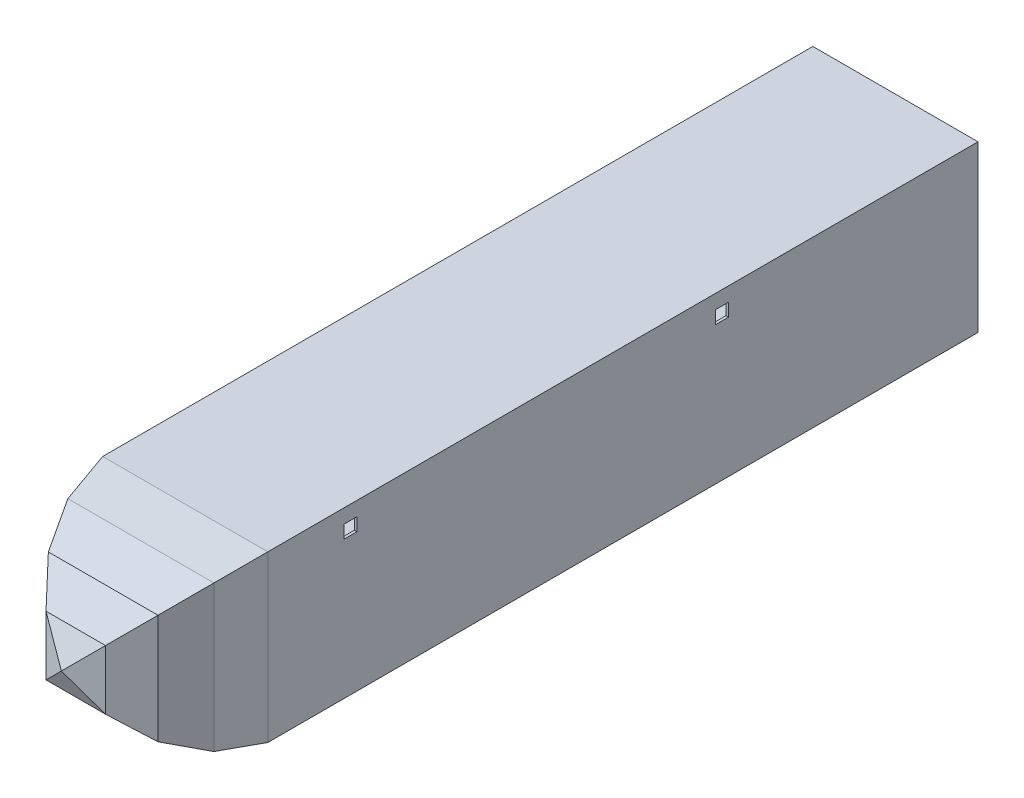
SolidWorks part; units mm, degrees
ref_plane "Front Plane" through (0, 0, 0) normal (0, 0, 1) x (1, 0, 0)
ref_plane "Top Plane" through (0, 0, 0) normal (0, 1, 0) x (1, 0, 0)
ref_plane "Right Plane" through (0, 0, 0) normal (1, 0, 0) x (0, 0, -1)
sketch "Sketch1" plane through (0, 0, 0) normal (0, 0, 1) x (1, 0, 0)
  line L1 (-50.8, -50.8) -> (50.8, -50.8)
  line L2 (-50.8, -50.8) -> (-50.8, 50.8)
  line L3 (-50.8, 50.8) -> (50.8, 50.8)
  line L4 (50.8, -50.8) -> (50.8, 50.8)
  line L5 (-50.8, -50.8) -> (50.8, 50.8) construction
  line L6 (-50.8, 50.8) -> (50.8, -50.8) construction
  point P0 (0, 0)
  dimension "D1" = 101.6
  dimension "D2" = 101.6
extrude "Boss-Extrude1" add sketch "Sketch1" along normal blind 436.88 contours L2 L1 L4 L3
ref_plane "Plane1" through (0, 0, 464.1566) normal (0, 0, 1) x (1, 0, 0)
sketch "Sketch3" plane through (0, 0, 464.1566) normal (0, 0, 1) x (1, 0, 0)
  line L1 (-44.9132, -44.9132) -> (44.9132, -44.9132)
  line L2 (-44.9132, -44.9132) -> (-44.9132, 44.9132)
  line L3 (-44.9132, 44.9132) -> (44.9132, 44.9132)
  line L4 (44.9132, -44.9132) -> (44.9132, 44.9132)
  line L5 (-44.9132, -44.9132) -> (44.9132, 44.9132) construction
  line L6 (-44.9132, 44.9132) -> (44.9132, -44.9132) construction
  point P0 (0, 0)
  dimension "D1" = 89.8265
  dimension "D2" = 89.8265
sketch "Sketch5" plane through (0, 0, 436.88) normal (0, 0, 1) x (1, 0, 0)
  line L0 (50.8, -50.8) -> (50.8, 50.8) construction
  line L1 (-50.8, 50.8) -> (50.8, 50.8) construction
  line L2 (-50.8, -50.8) -> (-50.8, 50.8) construction
  line L3 (-50.8, -50.8) -> (50.8, -50.8) construction
  line L4 (50.8, -50.8) -> (50.8, 50.8)
  line L5 (-50.8, 50.8) -> (50.8, 50.8)
  line L6 (-50.8, -50.8) -> (-50.8, 50.8)
  line L7 (-50.8, -50.8) -> (50.8, -50.8)
loft "Loft2" add profiles "Sketch5", "Sketch3" connector at (-50.8, 50.8, 436.88) connector at (-44.9132, 44.9132, 464.1566)
ref_plane "Plane2" through (0, 0, 487.3594) normal (0, 0, 1) x (1, 0, 0)
sketch "Sketch6" plane through (0, 0, 487.3594) normal (0, 0, 1) x (1, 0, 0)
  line L1 (-33.7159, -33.7159) -> (33.7159, -33.7159)
  line L2 (-33.7159, -33.7159) -> (-33.7159, 33.7159)
  line L3 (-33.7159, 33.7159) -> (33.7159, 33.7159)
  line L4 (33.7159, -33.7159) -> (33.7159, 33.7159)
  line L5 (-33.7159, -33.7159) -> (33.7159, 33.7159) construction
  line L6 (-33.7159, 33.7159) -> (33.7159, -33.7159) construction
  point P0 (0, 0)
  dimension "D1" = 67.4318
  dimension "D2" = 67.4318
loft "Loft3" add profiles "Sketch3<6>", "Sketch6" connector at (-44.9132, 44.9132, 464.1566) connector at (-33.7159, 33.7159, 487.3594)
sketch "Sketch3<6>" plane through (0, 0, 464.1566) normal (0, 0, 1) x (1, 0, 0) same geometry as "Sketch3"
ref_plane "Plane3" through (0, 0, 504.2173) normal (0, 0, 1) x (1, 0, 0)
sketch "Sketch7" plane through (0, 0, 504.2173) normal (0, 0, 1) x (1, 0, 0)
  line L5 (-44.9132, -44.9132) -> (44.9132, 44.9132) construction
  line L6 (-18.3041, -18.3041) -> (18.3041, -18.3041)
  line L8 (-18.3041, -18.3041) -> (-18.3041, 18.3041)
  line L9 (-18.3041, 18.3041) -> (18.3041, 18.3041)
  line L10 (18.3041, -18.3041) -> (18.3041, 18.3041)
  line L11 (-18.3041, -18.3041) -> (18.3041, 18.3041) construction
  line L12 (-18.3041, 18.3041) -> (18.3041, -18.3041) construction
  point P1 (0, 0)
  dimension "D1" = 36.6083
  dimension "D2" = 36.6083
loft "Loft4" add profiles "Sketch6<4>", "Sketch7" connector at (33.7159, 33.7159, 487.3594) connector at (18.3041, 18.3041, 504.2173)
sketch "Sketch6<4>" plane through (0, 0, 487.3594) normal (0, 0, 1) x (1, 0, 0) same geometry as "Sketch6"
sketch3d "3DSketch1" plane through (0, 0, 0) normal (0, 0, 1) x (1, 0, 0)
  dimension "D1" = 8.8627
sketch "Sketch8" plane through (0, 0, 513.08) normal (0, 0, 1) x (1, 0, 0)
  point P0 (0, 0)
loft "Loft5" add profiles "Sketch8", "Sketch7<5>"
sketch "Sketch7<5>" plane through (0, 0, 504.2173) normal (0, 0, 1) x (1, 0, 0) same geometry as "Sketch7"
shell "Shell1" thickness 1.5875 removed face at (0, 0, 0)
sketch "Sketch9" plane through (50.8, 0, 0) normal (1, 0, 0) x (0, 0, -1)
  line L0 (-436.88, 50.8) -> (-436.88, 38.1)
  line L1 (-436.88, -50.8) -> (-436.88, 50.8) construction
  line L2 (-436.88, 38.1) -> (-386.08, 38.1)
  line L3 (-386.08, 38.1) -> (-157.48, 38.1)
  line L5 (-390.0805, 34.0995) -> (-382.0795, 34.0995)
  line L6 (-390.0805, 34.0995) -> (-390.0805, 42.1005)
  line L7 (-390.0805, 42.1005) -> (-382.0795, 42.1005)
  line L8 (-382.0795, 34.0995) -> (-382.0795, 42.1005)
  line L9 (-390.0805, 34.0995) -> (-382.0795, 42.1005) construction
  line L10 (-390.0805, 42.1005) -> (-382.0795, 34.0995) construction
  line L11 (-161.4805, 34.0995) -> (-153.4795, 34.0995)
  line L12 (-161.4805, 34.0995) -> (-161.4805, 42.1005)
  line L13 (-161.4805, 42.1005) -> (-153.4795, 42.1005)
  line L14 (-153.4795, 34.0995) -> (-153.4795, 42.1005)
  line L15 (-161.4805, 34.0995) -> (-153.4795, 42.1005) construction
  line L16 (-161.4805, 42.1005) -> (-153.4795, 34.0995) construction
  dimension "D4" = 8.001
  dimension "D5" = 8.001
  dimension "D1" = 12.7
  dimension "D2" = 50.8
  dimension "D3" = 228.6
  dimension "D6" = 8.001
  dimension "D7" = 8.001
extrude "Cut-Extrude1" cut sketch "Sketch9" against normal through all contours L5 L8 L3 L2 L6 | L3 L8 L7 L6 L2 | L11 L14 L13 L12 region at (50.8, 40.1002, 386.08) region at (50.8, 36.0997, 386.08) region at (50.8, 40.1002, 161.3673)
